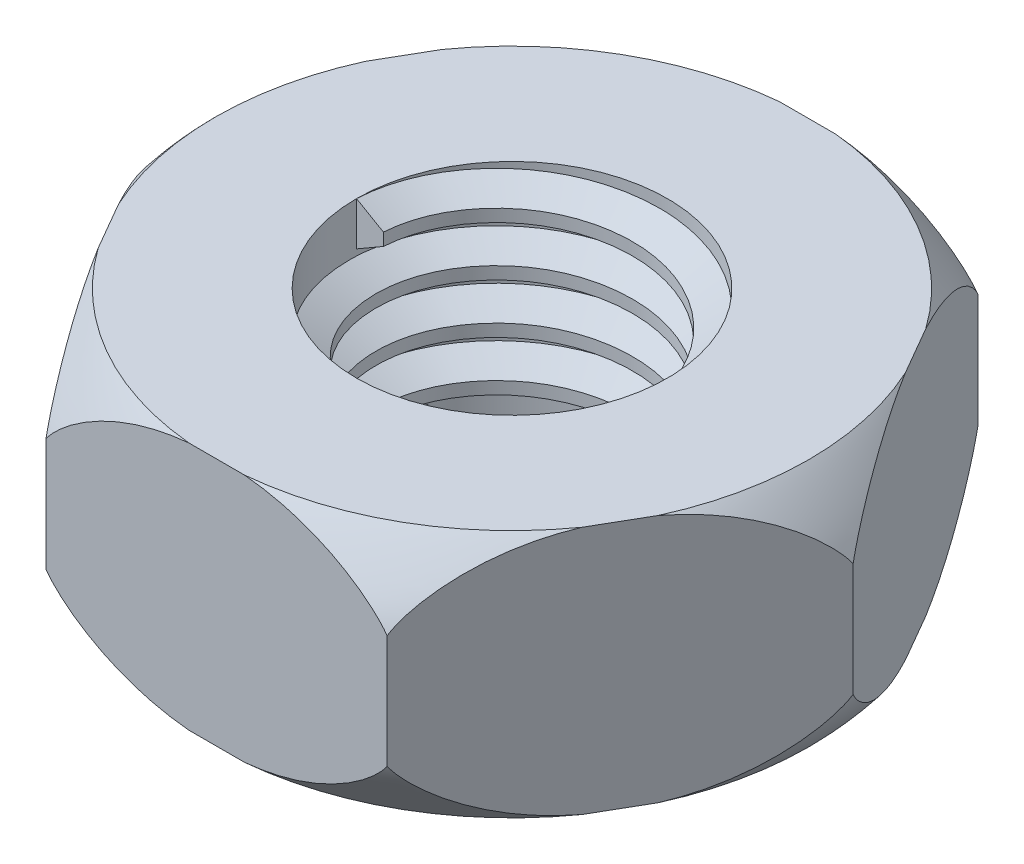
SolidWorks part; units mm, degrees
material "ASTM A36 Steel"
ref_plane "Front Plane" through (0, 0, 0) normal (0, 0, 1) x (1, 0, 0)
ref_plane "Top Plane" through (0, 0, 0) normal (0, 1, 0) x (1, 0, 0)
ref_plane "Right Plane" through (0, 0, 0) normal (1, 0, 0) x (0, 0, -1)
sketch "Sketch1" plane through (0, 0, 0) normal (0, 1, 0) x (1, 0, 0)
  line L1 (2.7424, -4.75) -> (5.4848, 0)
  line L2 (5.4848, 0) -> (2.7424, 4.75)
  line L3 (2.7424, 4.75) -> (-2.7424, 4.75)
  line L4 (-2.7424, 4.75) -> (-5.4848, 0)
  line L5 (-5.4848, 0) -> (-2.7424, -4.75)
  line L6 (-2.7424, -4.75) -> (2.7424, -4.75)
  circle A0 centre (0, 0) radius 4.75 construction
  circle A2 centre (0, 0) radius 6.5
  circle A3 centre (0, 0) radius 2.5
  point P12 (0, 0)
  dimension "D2" = 5
  dimension "D1" = 9.5
  dimension "D3" = 13
extrude "Boss-Extrude1" add sketch "Sketch1" against normal blind 2 contours L5 L6 L1 L2 L3 L4 A3
sketch "Sketch2" plane through (0, 0, 0) normal (0, 0, 1) x (1, 0, 0)
  line L1 (-5.4848, -0.9103) -> (-5.4848, -2)
  line L2 (-5.4848, -2) -> (-5.4848, 0) construction
  line L3 (-5.4848, -2) -> (-4.771, -2)
  line L4 (-5.4848, -2) -> (-2.7424, -2) construction
  line L6 (0, 0) -> (0, -3.8592) construction
  spline S0 degree 3 poles (-4.771, -2) (-4.9764, -1.7911) (-5.3423, -1.3056) (-5.4848, -0.9103) knots 0 0 0 0 0.941596 0.941596 0.941596 0.941596
  dimension "D1" = 1.0897
  dimension "D2" = 0.7138
revolve "Cut-Revolve1" cut sketch "Sketch2" angle 360 about L6
mirror "Mirror2" about plane through (0, 0, 0) normal (0, 1, 0) of "Boss-Extrude1", "Cut-Revolve1"
thread "Thread1" pitch 0.8 start angle 0, offset 0, length 0, pitch 0.8, diameter 5
ref_plane "Plane1" through (-2.5, 2, 0) normal (0, 0, 1) x (-1, 0, 0)
sketch "Thread Profile1" plane through (-2.5, 2, 0) normal (0, 0, 1) x (-1, 0, 0)
  line L0 (0, 0) -> (0, 0.8) construction
  line L11 (0, 0) -> (0, 0.7)
  line L12 (0, 0.7) -> (-0.433, 0.45)
  line L13 (-0.433, 0.45) -> (-0.433, 0.25)
  line L15 (-0.433, 0.25) -> (0, 0)
  line L17 (-0.433, 0.35) -> (0, 0.35) construction
  point P2 (0, 0)
  dimension "Pitch" = 0.8
  dimension "Profile_Angle" = 60
  dimension "Profile_Land" = 0.2
  dimension "Profile_Height" = 0.433
